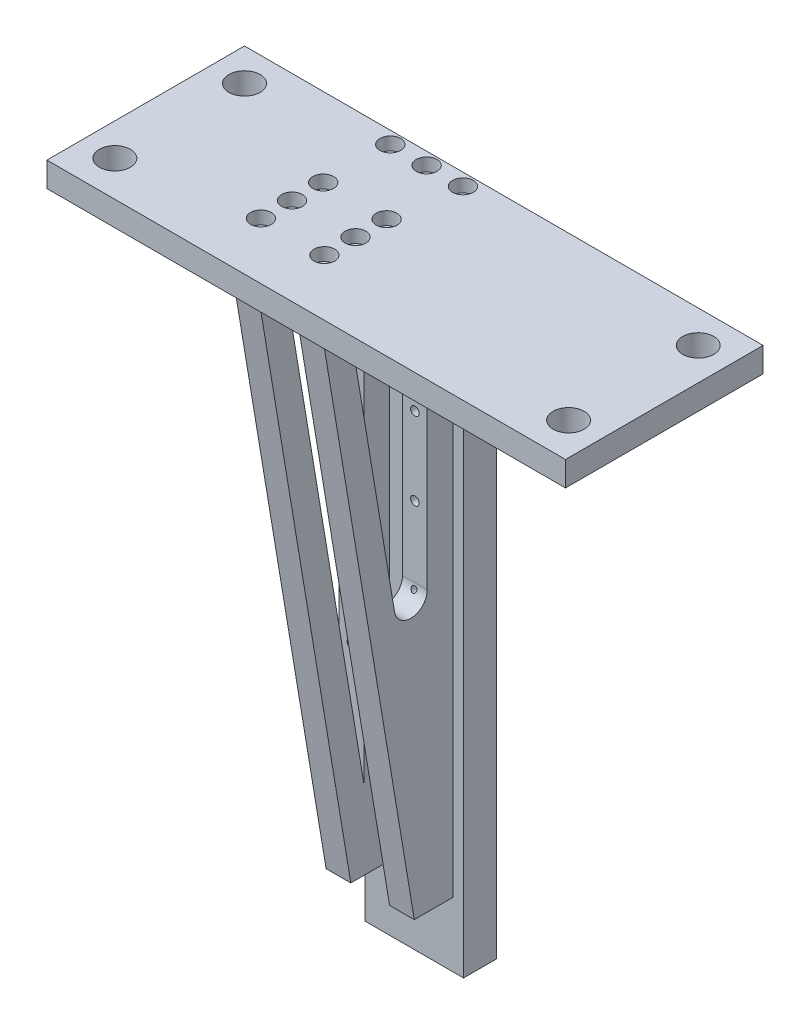
SolidWorks part; units mm, degrees
ref_plane "Front Plane" through (0, 0, 0) normal (0, 0, 1) x (1, 0, 0)
ref_plane "Top Plane" through (0, 0, 0) normal (0, 1, 0) x (1, 0, 0)
ref_plane "Right Plane" through (0, 0, 0) normal (1, 0, 0) x (0, 0, -1)
sketch "Sketch1" plane through (0, 0, 0) normal (1, 0, 0) x (0, 0, -1)
  line L0 (-66.675, 0) -> (9.525, 0)
  line L2 (0, 0) -> (9.525, 0)
  line L4 (9.525, 9.525) -> (-66.675, 9.525)
  line L5 (-66.675, 9.525) -> (-66.675, 0)
  line L7 (0, 0) -> (9.525, 0)
  line L8 (0, 0) -> (0, -250)
  line L9 (0, -250) -> (9.525, -250)
  line L10 (9.525, 0) -> (9.525, -250)
  line L16 (9.525, 9.525) -> (9.525, 0)
  line L19 (-66.675, 0) -> (-66.675, -3.175)
  line L20 (-66.675, -3.175) -> (9.525, -3.175)
  dimension "D1" = 9.525
  dimension "D2" = 9.525
  dimension "D3" = 76.2
  dimension "D5" = 250
  dimension "D7" = 12.7
extrude "Boss-Extrude5" add sketch "Sketch1" along normal blind 125 and the other way blind 75 contours L16 L4 L5 L0 region at (0, 4.7625, 28.575)
extrude "Boss-Extrude6" add sketch "Sketch1<5>" along normal mid plane 38 separate body contours L10 L0 L8 L9 | L8 L20 L10 L0 region at (0, -1.5875, -4.7625) region at (0, -126.5875, -4.7625)
sketch "Sketch1<5>" plane through (0, 0, 0) normal (1, 0, 0) x (0, 0, -1) same geometry as "Sketch1"
sketch "Sketch2" plane through (0, 0, -9.525) normal (0, 0, -1) x (-1, 0, 0)
  line L0 (0, 0) -> (0, -263.8174) construction
  line L1 (-19, 0) -> (-15, 0)
  line L2 (-15, -4.5282) -> (15, -4.5282)
  line L3 (-15, -4.5282) -> (-15, -36.0894)
  line L4 (-15, -36.0894) -> (15, -36.0894)
  line L5 (15, -4.5282) -> (15, -36.0894)
  line L6 (-19, 0) -> (19, 0) construction
  line L7 (-15, 0) -> (-15, -250)
  line L8 (-19, -250) -> (19, -250) construction
  line L9 (-15, -250) -> (-19, -250)
  line L10 (-19, -250) -> (-19, 0)
  line M8 (19, 0) -> (-19, 0)
  line M9 (-19, 0) -> (-19, -250)
  line M10 (-19, -250) -> (19, -250)
  dimension "D1" = 30
  dimension "D2" = 4
extrude "Boss-Extrude7" add sketch "Sketch2" along normal blind 3.175 contours L7 L3 M8 M9 M10 region at (17, -125, -9.525)
sketch "Sketch6" plane through (0, 0, 0) normal (0, -1, 0) x (1, 0, 0)
  line L0 (19, 0) -> (-19, 0) construction
  line L1 (-10, 5) -> (10, 5)
  line L2 (-10, 5) -> (-10, 0)
  line L3 (-10, 0) -> (10, 0)
  line L4 (10, 5) -> (10, 0)
  line L5 (0, 0) -> (0, 18.4937) construction
  line L6 (0, -9.525) -> (0, 66.675) construction
  line L7 (19, 0) -> (19, -12.7) construction
  line L8 (19, -2.525) -> (24, -2.525)
  line L9 (19, -2.525) -> (19, -7.525)
  line L10 (19, -7.525) -> (24, -7.525)
  line L11 (24, -2.525) -> (24, -7.525)
  line L12 (-75, -9.525) -> (125, -9.525) construction
  dimension "D1" = 5
  dimension "D2" = 20
  dimension "D3" = 2
  dimension "D4" = 5
  dimension "D5" = 5
extrude "Boss-Extrude8" add sketch "Sketch6" along normal up to vertex (3.175 mm away) up to point (0, -3.175, 66.675)
sketch "Sketch3" plane through (0, 0, 0) normal (0, 1, 0) x (1, 0, 0)
  line L0 (0, 0) -> (0, 9.525) construction
  line L1 (-19, 4.7625) -> (19, 4.7625) construction
  line L2 (-19, 0) -> (-19, 9.525) construction
  line L3 (19, 0) -> (19, 12.7) construction
  line L4 (0, 8.8001) -> (0, 1.2807) construction
  circle A0 centre (-14, 4.7625) radius 2
  circle A1 centre (0, 4.7625) radius 2
  circle A2 centre (14, 4.7625) radius 2
  dimension "D1" = 4
  dimension "D2" = 14
sketch "Sketch7" plane through (0, 0, -9.525) normal (0, 0, -1) x (-1, 0, 0)
  line L0 (-15, 0) -> (-15, -250) construction
  line L1 (-15, -10.1116) -> (-5.475, -10.1116)
  line L2 (-15, -10.1116) -> (-15, -28.0084)
  line L3 (-15, -28.0084) -> (-5.475, -28.0084)
  line L4 (-5.475, -10.1116) -> (-5.475, -28.0084)
  line L5 (9.475, -9.6486) -> (19, -9.6486)
  line L6 (9.475, -9.6486) -> (9.475, -28.9758)
  line L7 (9.475, -28.9758) -> (19, -28.9758)
  line L8 (19, -9.6486) -> (19, -28.9758)
  line L9 (19, 0) -> (19, -250) construction
  point P8 (0, 0)
  dimension "D1" = 9.525
sketch "Sketch5" plane through (0, 0, 0) normal (1, 0, 0) x (0, 0, -1)
  line L0 (-50.8, 0) -> (-50.8, -10)
  line L1 (-25, 0) -> (-25, -8.65)
  line L2 (-50.8, -10) -> (-15, -225)
  line L3 (-15, -225) -> (0, -225)
  line L4 (0, 0) -> (0, -250) construction
  line L5 (0, -225) -> (0, 0)
  line L6 (0, 0) -> (-50.8, 0)
  line L7 (0, -250) -> (9.525, -250) construction
  line L8 (-66.675, 0) -> (9.525, 0) construction
  line L9 (-15, 0) -> (-15, -8.65)
  line L10 (-8.65, -15) -> (0, -15)
  line L11 (-8.65, -25) -> (0, -25)
  line L12 (-40.6623, -10) -> (-10, -194.1452)
  line L13 (-10, -194.1452) -> (-10, -194.1452)
  line L14 (-10, -194.1452) -> (-10, -24.9442)
  line L16 (-40.6623, -10) -> (-40.6623, -10)
  line L17 (-24.9442, -10) -> (-40.6623, -10)
  line L18 (-10, -10) -> (-40.6623, -10) construction
  line L19 (-10, -194.1452) -> (-10, -10) construction
  arc A0 (-15, -8.65) -> (-8.65, -15) centre (-8.65, -8.65) ccw
  arc A1 (-25, -8.65) -> (-8.65, -25) centre (-8.65, -8.65) ccw
  point P18 (-15, -15)
  dimension "D8" = 6.35
  dimension "D1" = 50.8
  dimension "D2" = 15
  dimension "D3" = 25
  dimension "D4" = 10
  dimension "D5" = 225
  dimension "D6" = 15
  dimension "D7" = 15
  dimension "D9" = 10
  dimension "D10" = 10
extrude "Boss-Extrude9" add sketch "Sketch5" along normal up to vertex (15 mm away) from vertex separate body contours L10 L9 L6 L0 L2 L3 L5 | L1 A1 L11 L5 L10 A0 L9 L6 region at (0, -2.3066, 37.9) region at (0, -14.2842, 14.2842) up to point (15, -28.0084, -9.525) starting at point (5.475, -28.0084, -9.525)
extrude "Boss-Extrude10" add sketch "Sketch5<3>" against normal up to vertex (19 mm away) from vertex separate body contours L10 L9 L6 L0 L2 L3 L5 | L1 A1 L11 L5 L10 A0 L9 L6 region at (0, -2.3066, 37.9) region at (0, -14.2842, 14.2842) up to point (-19, -9.6486, -9.525) starting at point (-9.475, -9.6486, -9.525)
sketch "Sketch5<3>" plane through (0, 0, 0) normal (1, 0, 0) x (0, 0, -1) same geometry as "Sketch5"
fillet "Fillet1" radius 6.35 4 edges at (10.2375, -194.1452, 10) (10.2375, -24.9442, 10) (10.2375, -10, 24.9442) (10.2375, -10, 40.6623)
ref_plane "Plane1" through (-2, 0, 0) normal (1, 0, 0) x (0, 0, -1)
sketch "Sketch8" plane through (0, 0, 0) normal (0, 1, 0) x (1, 0, 0)
  line L0 (10.2375, -15) -> (10.2375, -50.8) construction
  line L1 (15, -15) -> (5.475, -15) construction
  line L2 (15, -50.8) -> (5.475, -50.8) construction
  line L3 (5.475, -32.9) -> (15, -32.9) construction
  line L4 (5.475, -15) -> (5.475, -50.8) construction
  line L5 (15, -15) -> (15, -50.8) construction
  line L7 (-2, 31.7466) -> (-2, -84.8925) construction
  line L8 (-2, -27.94) -> (-2, 27.94) construction
  circle A0 centre (10.2375, -20.9) radius 3
  circle A1 centre (10.2375, -32.9) radius 3
  circle A2 centre (10.2375, -44.9) radius 3
  circle A3 centre (-14.2375, -44.9) radius 3
  circle A4 centre (-14.2375, -32.9) radius 3
  circle A5 centre (-14.2375, -20.9) radius 3
  dimension "D2" = 6
  dimension "D1" = 12
sketch "Sketch9" plane through (0, 0, 0) normal (0, 0, -1) x (-1, 0, 0)
  line L0 (-10.2375, -15) -> (-10.2375, -225) construction
  line L1 (-15, -15) -> (-5.475, -15) construction
  line L2 (-15, -225) -> (-5.475, -225) construction
  line L3 (-10.2375, -120) -> (-10.2375, -90) construction
  line L4 (2, -22.6495) -> (2, -218.2945) construction
  line L5 (2, 27.94) -> (2, -27.94) construction
  circle A0 centre (-10.2375, -120) radius 3
  circle A1 centre (-10.2375, -150) radius 3
  circle A2 centre (-10.2375, -180) radius 3
  circle A3 centre (-10.2375, -210) radius 3
  circle A16 centre (-10.2375, -90) radius 3
  circle A17 centre (-10.2375, -60) radius 3
  circle A18 centre (-10.2375, -30) radius 3
  circle A19 centre (14.2375, -210) radius 3
  circle A20 centre (14.2375, -180) radius 3
  circle A21 centre (14.2375, -150) radius 3
  circle A22 centre (14.2375, -120) radius 3
  circle A23 centre (14.2375, -90) radius 3
  circle A24 centre (14.2375, -60) radius 3
  circle A25 centre (14.2375, -30) radius 3
  dimension "D1" = 6
  dimension "D4" = 30
  dimension "D5" = 4
  dimension "D6" = 30
  dimension "D2" = 4
  dimension "D3" = 1
hole_wizard "CBORE for M4 SHCS1" positions "Sketch12" profile "Sketch13" counterbore size "M4" standard "ANSI Metric" end condition through all
sketch "Sketch12" plane through (0, 0, -9.525) normal (0, 0, -1) x (-1, 0, 0)
  line L0 (-10.2375, -15) -> (-10.2375, -225) construction
  point P0 (-10.2375, -60)
  point P3 (-10.2375, -30)
  point P6 (-10.2375, -90)
  point P9 (-10.2375, -120)
  point P13 (-10.2375, -150)
  point P16 (-10.2375, -180)
  point P19 (-10.2375, -210)
  point P22 (14.2375, -210)
  point P25 (14.2375, -180)
  point P28 (14.2375, -150)
  point P31 (14.2375, -120)
  point P34 (14.2375, -90)
  point P37 (14.2375, -60)
  point P40 (14.2375, -30)
sketch "Sketch13" plane through (10.2375, -60, -9.525) normal (1, 0, 0) x (0, 1, 0)
  line L0 (0, 0) -> (0, 76.2)
  line L1 (0, 76.2) -> (2.4, 76.2)
  line L3 (2.4, 76.2) -> (2.4, 5)
  line L4 (2.4, 5) -> (4, 5)
  line L5 (4, 5) -> (4, 0)
  line L7 (4, 0) -> (0, 0)
  line L11 (0, -6.35) -> (0, 107.95) construction
  dimension "Thru Hole Dia." = 4.8
  dimension "Thru Hole Depth" = 76.2
  dimension "C'Bore Dia." = 8
  dimension "C'Bore Depth" = 5
hole_wizard "CBORE for M4 SHCS2" positions "Sketch14" profile "Sketch15" counterbore size "M4" standard "ANSI Metric" end condition through all
sketch "Sketch14" plane through (0, 9.525, 0) normal (0, 1, 0) x (1, 0, 0)
  line L0 (-19, 4.7625) -> (19, 4.7625) construction
  point P0 (-14.2375, -20.9)
  point P3 (-14.2375, -32.9)
  point P6 (-14.2375, -44.9)
  point P9 (10.2375, -44.9)
  point P12 (10.2375, -32.9)
  point P15 (10.2375, -20.9)
  point P18 (14, 4.7625)
  point P21 (0, 4.7625)
  point P25 (-14, 4.7625)
sketch "Sketch15" plane through (-14.2375, 9.525, 20.9) normal (1, 0, 0) x (0, 0, 1)
  line L0 (0, 0) -> (0, 259.525)
  line L1 (0, 259.525) -> (2.4, 259.525)
  line L3 (2.4, 259.525) -> (2.4, 5)
  line L4 (2.4, 5) -> (4, 5)
  line L5 (4, 5) -> (4, 0)
  line L7 (4, 0) -> (0, 0)
  line L11 (0, -6.35) -> (0, 107.95) construction
  dimension "Thru Hole Dia." = 4.8
  dimension "Thru Hole Depth" = 259.525
  dimension "C'Bore Dia." = 8
  dimension "C'Bore Depth" = 5
hole_wizard "M4x0.7 Tapped Hole1" positions "Sketch16" profile "Sketch17" tap size "M4x0.7" standard "ANSI Metric"
sketch "Sketch16" plane through (0, 0, 0) normal (0, 1, 0) x (1, 0, 0)
  line L0 (-19, 4.7625) -> (19, 4.7625) construction
  point P0 (10.2375, -20.9)
  point P3 (10.2375, -32.9)
  point P6 (10.2375, -44.9)
  point P9 (-14.2375, -44.9)
  point P12 (-14.2375, -32.9)
  point P15 (-14.2375, -20.9)
  point P19 (-14, 4.7625)
  point P22 (0, 4.7625)
  point P26 (14, 4.7625)
sketch "Sketch17" plane through (10.2375, 0, 20.9) normal (1, 0, 0) x (0, 0, 1)
  line L0 (0, 0) -> (0, 11.0914)
  line L1 (0, 11.0914) -> (1.65, 10.1)
  line L2 (1.65, 10.1) -> (1.65, 0)
  line L5 (1.65, 0) -> (0, 0)
  line L10 (0, 11.0914) -> (-1.65, 10.1) construction
  line L11 (0, -6.35) -> (0, 107.95) construction
  dimension "Tap Drill Dia." = 3.3
  dimension "Tap Drill Depth" = 10.1
  dimension "Drill Angle" = 118
hole_wizard "M4x0.7 Tapped Hole2" positions "Sketch18" profile "Sketch19" tap size "M4x0.7" standard "ANSI Metric"
sketch "Sketch18" plane through (0, 0, 0) normal (0, 0, -1) x (-1, 0, 0)
  line L0 (-10.2375, -15) -> (-10.2375, -225) construction
  point P0 (-10.2375, -30)
  point P3 (14.2375, -30)
  point P6 (14.2375, -60)
  point P9 (-10.2375, -60)
  point P12 (-10.2375, -90)
  point P15 (14.2375, -90)
  point P18 (-10.2375, -120)
  point P22 (14.2375, -120)
  point P25 (-10.2375, -150)
  point P28 (14.2375, -150)
  point P31 (-10.2375, -180)
  point P34 (14.2375, -180)
  point P37 (-10.2375, -210)
  point P40 (14.2375, -210)
sketch "Sketch19" plane through (10.2375, -30, 0) normal (1, 0, 0) x (0, 1, 0)
  line L0 (0, 0) -> (0, 11.0914)
  line L1 (0, 11.0914) -> (1.65, 10.1)
  line L2 (1.65, 10.1) -> (1.65, 0)
  line L5 (1.65, 0) -> (0, 0)
  line L10 (0, 11.0914) -> (-1.65, 10.1) construction
  line L11 (0, -6.35) -> (0, 107.95) construction
  dimension "Tap Drill Dia." = 3.3
  dimension "Tap Drill Depth" = 10.1
  dimension "Drill Angle" = 118
sketch "Sketch20" plane through (0, 9.525, 0) normal (0, 1, 0) x (1, 0, 0)
  line L0 (25, 9.525) -> (25, -66.675) construction
  line L1 (-75, 9.525) -> (125, 9.525) construction
  line L2 (-75, -66.675) -> (125, -66.675) construction
  line L3 (-75, 9.525) -> (-75, -66.675) construction
  circle A0 centre (-62.5, -2.975) radius 5
  circle A1 centre (-62.5, -52.975) radius 5
  circle A2 centre (112.5, -52.975) radius 5
  circle A3 centre (112.5, -2.975) radius 5
  dimension "D1" = 10
  dimension "D2" = 12.5
  dimension "D3" = 12.5
  dimension "D4" = 50
hole_wizard "M10 Clearance Hole1" positions "Sketch21" profile "Sketch22" hole size "M10" standard "ANSI Metric" end condition through all
sketch "Sketch21" plane through (0, 9.525, 0) normal (0, 1, 0) x (1, 0, 0)
  point P0 (-62.5, -2.975)
  point P3 (-62.5, -52.975)
  point P6 (112.5, -52.975)
  point P9 (112.5, -2.975)
sketch "Sketch22" plane through (-62.5, 9.525, 2.975) normal (1, 0, 0) x (0, 0, 1)
  line L0 (0, 0) -> (0, 259.525)
  line L1 (0, 259.525) -> (6, 259.525)
  line L2 (6, 259.525) -> (6, 0)
  line L5 (6, 0) -> (0, 0)
  line L11 (0, -6.35) -> (0, 107.95) construction
  dimension "Thru Hole Dia." = 12
  dimension "Thru Hole Depth" = 259.525
